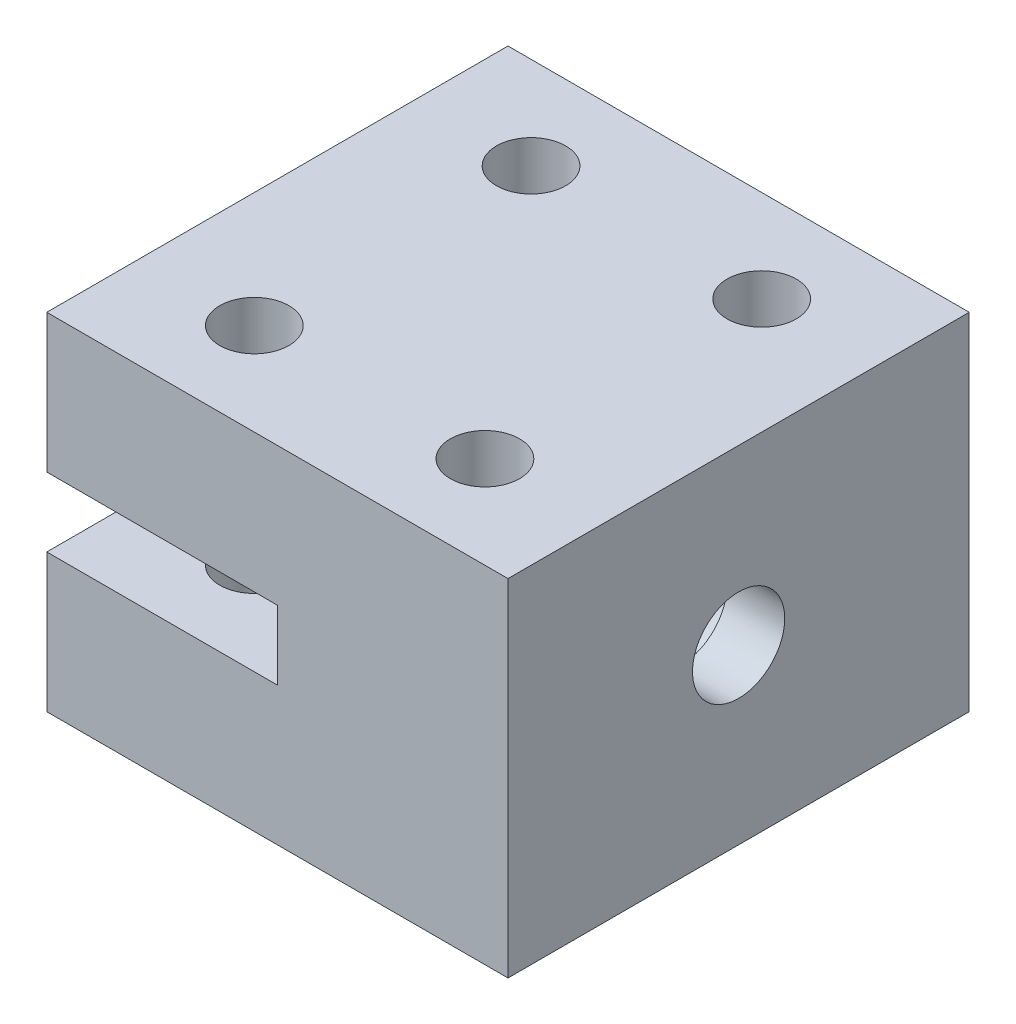
SolidWorks part; units mm, degrees
ref_plane "Front Plane" through (0, 0, 0) normal (0, 0, 1) x (1, 0, 0)
ref_plane "Top Plane" through (0, 0, 0) normal (0, 1, 0) x (1, 0, 0)
ref_plane "Right Plane" through (0, 0, 0) normal (1, 0, 0) x (0, 0, -1)
sketch "Sketch1" plane through (0, 0, 0) normal (0, 1, 0) x (1, 0, 0)
  line L5 (-10, 10) -> (10, 10)
  line L6 (-10, 10) -> (-10, -10)
  line L7 (-10, -10) -> (10, -10)
  line L8 (10, 10) -> (10, -10)
  line L9 (-10, 10) -> (10, -10) construction
  line L10 (-10, -10) -> (10, 10) construction
  point P1 (0, 0)
  dimension "D1" = 20
  dimension "D2" = 20
extrude "Boss-Extrude1" add sketch "Sketch1" along normal mid plane 15
extrude "Cut-Extrude2" cut sketch "Sketch1<3>" against normal mid plane 3
sketch "Sketch1<3>" plane through (0, 0, 0) normal (0, 1, 0) x (1, 0, 0) same geometry as "Sketch1"
sketch "Sketch3" plane through (0, 0, 0) normal (0, 1, 0) x (1, 0, 0)
  line L0 (10, 10) -> (-10, 10) construction
  line L1 (0, 10) -> (10, 10)
  line L2 (0, 10) -> (0, -10)
  line L3 (0, -10) -> (10, -10)
  line L4 (10, 10) -> (10, -10)
extrude "Boss-Extrude2" add sketch "Sketch3" along normal mid plane 3
sketch "Sketch5" plane through (0, 0, 0) normal (0, 1, 0) x (1, 0, 0)
  line L1 (-5, 6) -> (5, 6) construction
  line L2 (-5, 6) -> (-5, -6) construction
  line L3 (-5, -6) -> (5, -6) construction
  line L4 (5, 6) -> (5, -6) construction
  line L5 (-5, 6) -> (5, -6) construction
  line L6 (-5, -6) -> (5, 6) construction
  circle A0 centre (-5, 6) radius 1.5
  circle A1 centre (5, 6) radius 1.5
  circle A2 centre (5, -6) radius 1.5
  circle A3 centre (-5, -6) radius 1.5
  point P0 (0, 0)
  dimension "D3" = 3
  dimension "D1" = 10
  dimension "D2" = 12
extrude "mounthole" cut sketch "Sketch5" against normal through all both and the other way through all
fillet "Fillet1" [suppressed] radius 1
ref_plane "Plane1" through (5, 0, 0) normal (1, 0, 0) x (0, 0, -1)
sketch "Sketch6" plane through (5, 0, 0) normal (1, 0, 0) x (0, 0, -1)
  circle A0 centre (0, 0) radius 3.5
  dimension "D1" = 7
extrude "bearinghole" cut sketch "Sketch6" along normal blind 2.5
sketch "Sketch4" plane through (10, 0, 0) normal (1, 0, 0) x (0, 0, -1)
  circle A0 centre (0, 0) radius 2
  dimension "D1" = 4
extrude "shaft" cut sketch "Sketch4" against normal blind 5
